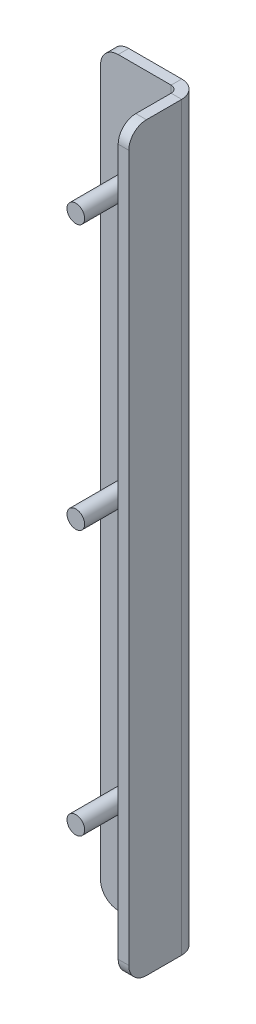
SolidWorks part; units mm, degrees
note: The reader was unsure of these and kept them because the rebuilt part matched: thickness of "基体-法兰1", "边线-法兰1", "钣金6", "钣金7", "钣金9", "钣金10"; flange length of "边线-法兰1".
ref_plane "前视基准面" through (0, 0, 0) normal (0, 0, 1) x (1, 0, 0)
ref_plane "上视基准面" through (0, 0, 0) normal (0, 1, 0) x (1, 0, 0)
ref_plane "右视基准面" through (0, 0, 0) normal (1, 0, 0) x (0, 0, -1)
sketch "草图1" plane through (0, 0, 0) normal (0, 0, 1) x (1, 0, 0)
  line L1 (-12.5, 105) -> (12.5, 105)
  line L2 (-12.5, 105) -> (-12.5, -105)
  line L3 (-12.5, -105) -> (12.5, -105)
  line L4 (12.5, 105) -> (12.5, -105)
  line L5 (-12.5, 105) -> (12.5, -105) construction
  line L6 (-12.5, -105) -> (12.5, 105) construction
  point P0 (0, 0)
  dimension "D1" = 25
  dimension "D2" = 210
base flange "基体-法兰1" sketch "草图1" thickness 3 reverse thickness direction no parameters "D1"=2
edge flange "边线-法兰1" sketch "草图8" flange angle 90 flange length 20 flange position material inside bend radius 2 thickness 3 relief rectangular parameters "D6"=10
sketch "草图8" plane through (12.5, 0, 0) normal (1, 0, 0) x (0, 1, 0)
  line L0 (-105, 0) -> (105, 0) construction
  line L1 (-105, 0) -> (105, 0)
  line L2 (-105, 0) -> (-105, 17)
  line L3 (-105, 17) -> (105, 17)
  line L4 (105, 17) -> (105, 0)
bend "边线折弯1" bend radius 2 bend angle 90 parameters "D5"=1
sketch "草图9" plane through (0, 0, 0) normal (0, 0, 1) x (1, 0, 0)
  line L0 (-4.5, -75) -> (-4.5, 75) construction
  line L1 (-4.5, 75) -> (-4.5, 77.5) construction
  line L2 (-4.5, -75) -> (-4.5, -77.5) construction
  line L3 (-12.5, 0) -> (-4.5, 0) construction
  line L4 (-12.5, 105) -> (-12.5, -105) construction
  circle A0 centre (-4.5, 0) radius 2.5
  circle A1 centre (-4.5, -75) radius 2.5
  circle A2 centre (-4.5, 75) radius 2.5
  point P4 (0, 0)
  dimension "D2" = 5
  dimension "D3" = 8
  dimension "D1" = 150
extrude "凸台-拉伸1" add sketch "草图9" along normal blind 15
fillet "圆角1" radius 5 4 edges at (11, 105, 17) (-12.5, 105, -1.5) (11, -105, 17) (-12.5, -105, -1.5)
sketch "折弯-线1" plane through (0, 0, 0) normal (0, 1, 0) x (1, 0, 0)
sketch "边界框1" plane through (0, 0, 0) normal (0, 1, 0) x (1, 0, 0)
sheet metal parameters "钣金6" thickness 3 parameters "D1"=2, "D7"=2
flat pattern "平板型式6" [suppressed]
sketch "折弯-线2" plane through (0, 0, 0) normal (0, 1, 0) x (1, 0, 0)
sketch "边界框2" [suppressed] plane through (0, 0, 0) normal (0, 1, 0) x (1, 0, 0)
sheet metal parameters "钣金7" thickness 3 parameters "D1"=2, "D7"=2
flat pattern "平板型式6" [suppressed]
sketch "折弯-线2" plane through (0, 0, 0) normal (0, 1, 0) x (1, 0, 0)
sketch "边界框2" [suppressed] plane through (0, 0, 0) normal (0, 1, 0) x (1, 0, 0)
bend of the flat pattern "展开-<边线折弯1>1"
sheet metal parameters "钣金9" thickness 3 parameters "D1"=2, "D7"=2
flat pattern "平板型式6"
sketch "折弯-线2" plane through (0, 0, 0) normal (0, 1, 0) x (1, 0, 0)
sketch "边界框2" [suppressed] plane through (0, 0, 0) normal (0, 1, 0) x (1, 0, 0)
sheet metal parameters "钣金10" thickness 3 parameters "D1"=2, "D7"=2
flat pattern "平板型式6" [suppressed]
sketch "折弯-线2" plane through (0, 0, 0) normal (0, 1, 0) x (1, 0, 0)
sketch "边界框2" [suppressed] plane through (0, 0, 0) normal (0, 1, 0) x (1, 0, 0)
bend of the flat pattern "展开-<边线折弯1>2"
